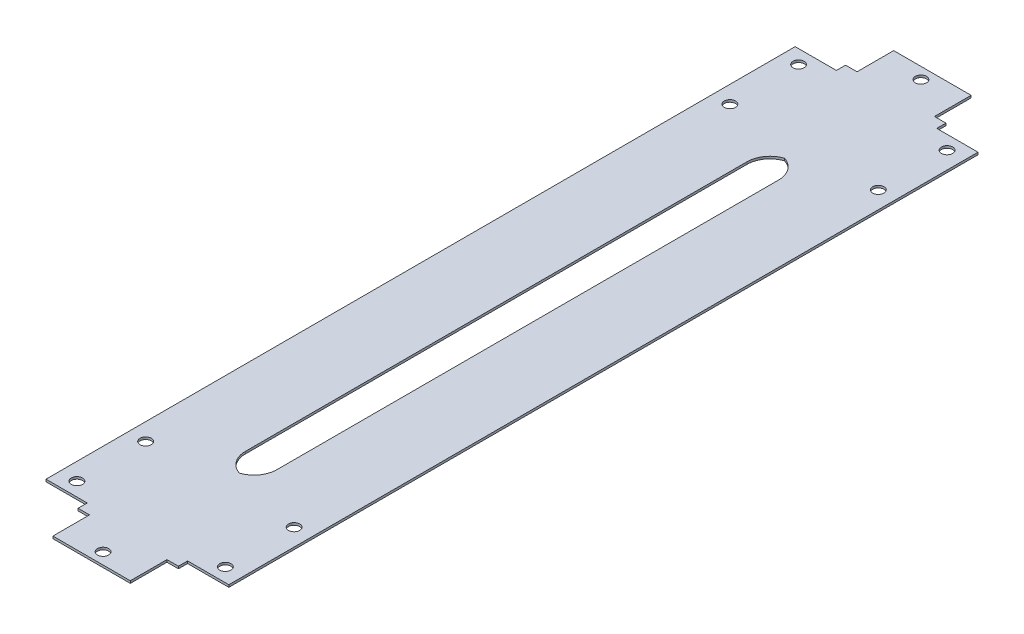
SolidWorks part; units mm, degrees
ref_plane "Front Plane" through (0, 0, 0) normal (0, 0, 1) x (1, 0, 0)
ref_plane "Top Plane" through (0, 0, 0) normal (0, 1, 0) x (1, 0, 0)
ref_plane "Right Plane" through (0, 0, 0) normal (1, 0, 0) x (0, 0, -1)
sketch "Sketch1" plane through (0, 0, 0) normal (0, 1, 0) x (1, 0, 0)
  line L0 (0, 0) -> (0, 163.5) construction
  line L1 (-39.9, -163.5) -> (-21.9, -163.5)
  line L3 (-21.9, 163.5) -> (-39.9, 163.5)
  line L4 (-39.9, 163.5) -> (-39.9, -163.5)
  line L16 (21.9, -163.5) -> (39.9, -163.5)
  line L17 (39.9, -163.5) -> (39.9, 163.5)
  line L25 (39.9, 163.5) -> (21.9, 163.5)
  line L26 (21.9, 163.5) -> (21.9, -163.5) construction
  line L27 (-6.9, 0) -> (0, 0) construction
  line L28 (-21.9, 163.5) -> (-21.9, 167.5)
  line L31 (-21.9, -163.5) -> (21.9, -163.5) construction
  line L32 (-21.9, 167.5) -> (-16.9, 167.5)
  line L33 (-16.9, 167.5) -> (-16.9, 183.5)
  line L35 (-21.9, 163.5) -> (21.9, 163.5) construction
  line L37 (-21.9, -163.5) -> (-21.9, 163.5) construction
  line L38 (0, 0) -> (6.9, 0) construction
  line L39 (-16.9, 183.5) -> (16.9, 183.5)
  line L40 (16.9, 183.5) -> (16.9, 167.5)
  line L41 (-6.9, 0) -> (-39.9, 0) construction
  line L42 (-6.9, 119.5) -> (6.9, 119.5)
  line L43 (-6.9, 119.5) -> (-6.9, -119.5)
  line L44 (-6.9, -119.5) -> (6.9, -119.5)
  line L45 (6.9, 119.5) -> (6.9, -119.5)
  line L46 (-6.9, 119.5) -> (6.9, -119.5) construction
  line L47 (-6.9, -119.5) -> (6.9, 119.5) construction
  line L48 (32.4, -127.5) -> (-32.4, -127.5) construction
  line L49 (32.4, -127.5) -> (32.4, 127.5) construction
  line L50 (32.4, 127.5) -> (-32.4, 127.5) construction
  line L51 (-32.4, -127.5) -> (-32.4, 127.5) construction
  line L52 (32.4, -127.5) -> (-32.4, 127.5) construction
  line L53 (32.4, 127.5) -> (-32.4, -127.5) construction
  line L54 (32.4, 157.5) -> (-32.4, 157.5) construction
  line L55 (32.4, 157.5) -> (32.4, -157.5) construction
  line L56 (32.4, -157.5) -> (-32.4, -157.5) construction
  line L57 (-32.4, 157.5) -> (-32.4, -157.5) construction
  line L58 (32.4, 157.5) -> (-32.4, -157.5) construction
  line L59 (32.4, -157.5) -> (-32.4, 157.5) construction
  line L60 (6.9, 0) -> (39.9, 0) construction
  line L61 (16.9, 167.5) -> (21.9, 167.5)
  line L62 (21.9, 167.5) -> (21.9, 163.5)
  line L63 (-16.9, 167.5) -> (16.9, 167.5) construction
  line L64 (0, 163.5) -> (0, 167.5) construction
  line L65 (-21.9, -163.5) -> (-21.9, -167.5)
  line L66 (-21.9, -167.5) -> (-16.9, -167.5)
  line L67 (-16.9, -167.5) -> (-16.9, -183.5)
  line L68 (-16.9, -183.5) -> (16.9, -183.5)
  line L69 (16.9, -183.5) -> (16.9, -167.5)
  line L70 (16.9, -167.5) -> (21.9, -167.5)
  line L71 (21.9, -167.5) -> (21.9, -163.5)
  line L72 (-16.9, -167.5) -> (16.9, -167.5) construction
  line L73 (0, -183.5) -> (0, -178.5) construction
  line L74 (0, 167.5) -> (0, 178.5) construction
  line L75 (0, 178.5) -> (0, 183.5) construction
  line L76 (0, -178.5) -> (0, -167.5) construction
  line L77 (0, -167.5) -> (0, -163.5) construction
  line L78 (0, -163.5) -> (0, 0) construction
  circle A2 centre (-32.4, 127.5) radius 2.45
  circle A3 centre (32.4, 127.5) radius 2.45
  circle A4 centre (-32.4, -127.5) radius 2.45
  circle A5 centre (32.4, -127.5) radius 2.45
  circle A6 centre (-32.4, -157.5) radius 2.45
  circle A7 centre (32.4, -157.5) radius 2.45
  circle A8 centre (32.4, 157.5) radius 2.45
  circle A9 centre (-32.4, 157.5) radius 2.45
  circle A10 centre (0, 178.5) radius 2.45
  circle A11 centre (0, -178.5) radius 2.45
  point P0 (0, 0)
  point P37 (0, 0)
  point P40 (0, 0)
  dimension "D12" = 4.9
  dimension "D5" = 30
  dimension "D15" = 64.8
  dimension "D3" = 10.5
  dimension "D14" = 10.5
  dimension "D4" = 18
  dimension "D16" = 18
  dimension "D18" = 4
  dimension "D11" = 38
  dimension "D7" = 10
  dimension "D6" = 21
  dimension "D9" = 4
  dimension "D19" = 33.8
  dimension "D20" = 5
  dimension "D8" = 43.8
  dimension "D13" = 315
  dimension "D17" = 335
  dimension "D21" = 327
  dimension "D10" = 15
extrude "Boss-Extrude1" add sketch "Sketch1" along normal blind 1
fillet "Fillet2" radius 10 4 edges at (6.9, 0.5, -119.5) (-6.9, 0.5, -119.5) (6.9, 0.5, 119.5) (-6.9, 0.5, 119.5)
equation "\"skin_sheetmetal_thickness\"= 0.80"
equation "\"base_width_skin_spacer\" = \"base_width_skin_target_width\" - 4 * \"skin_sheetmetal_thickness\" - 2 * \"base_width_skin_target_bend_radius\""
equation "\"base_width_skin_inner\" = \"base_width_skin_spacer\" + 2 * \"skin_sheetmetal_thickness\""
equation "\"base_width_skin_outer\" = \"base_width_skin_inner\" + 2 * \"skin_sheetmetal_thickness\""
equation "\"bend_cut_width\"= 3"
equation "\"bend_cut_length\"= 3"
equation "\"bend_offset_inner\"= 12.5"
equation "\"bend_offset_outer\" = \"bend_offset_inner\" + \"skin_sheetmetal_thickness\""
equation "\"border_offset_ends\"= 20"
equation "\"border_offset_sides\"= 10"
equation "\"border_offset_flange_horiz\"= 10"
equation "\"rivet_size\"= 4.3"
equation "\"rivet_offset_ends\"= \"rivet_spacing_horiz\"/2 - \"border_offset_ends\""
equation "\"rivet_spacing_horiz\"= 200"
equation "\"rivet_spacing_vert\"= 30"
equation "\"rivet_spacing_offset_right\"= 40"
equation "\"base_length\"= 200"
equation "\"D8@Sketch1\"=\"base_width_skin_spacer\""
equation "\"D19@Sketch1\"=\"base_width_skin_spacer\" - 10"
equation "\"D5@Sketch1\"=\"rivet_spacing_vert\""
equation "\"base_width_skin_spacer_length\" = 315"
equation "\"D13@Sketch1\"=\"base_width_skin_spacer_length\""
equation "\"bend_offset_spacer_tab\"= 21.0"
equation "\"D6@Sketch1\"=\"bend_offset_spacer_tab\""
equation "\"base_width_skin_target_width\" = 50"
equation "\"base_width_skin_target_bend_radius\" = 1.5"
